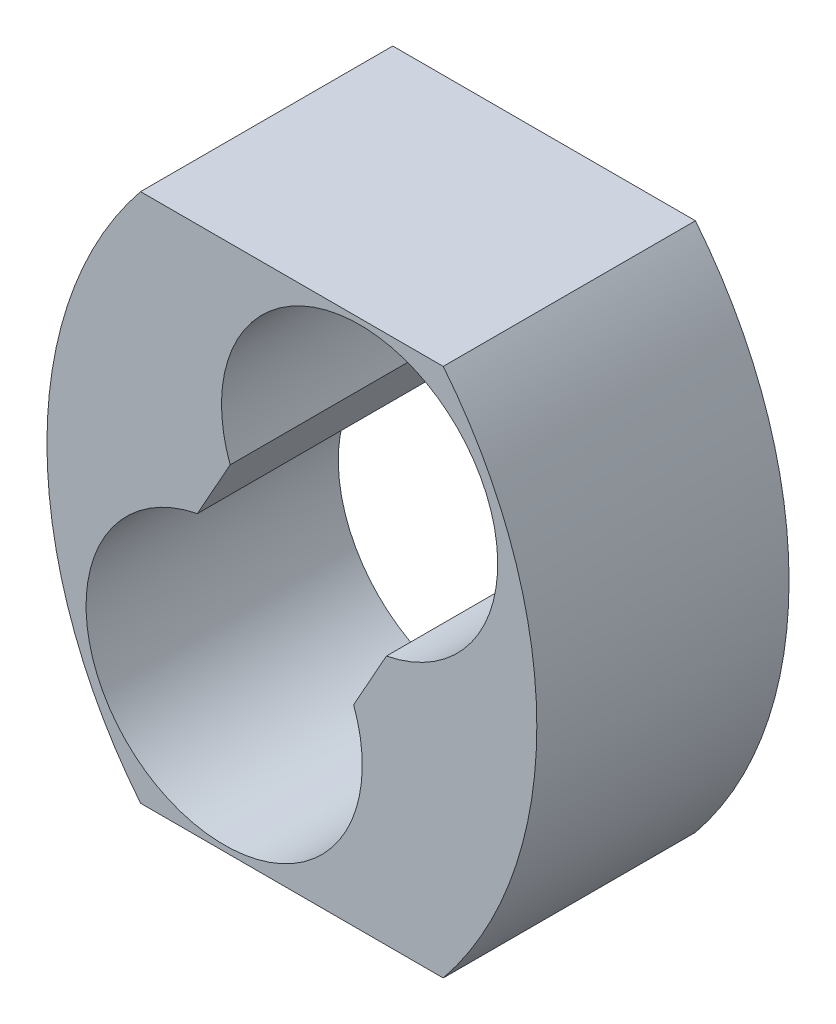
SolidWorks part; units mm, degrees
ref_plane "Alzado" through (0, 0, 0) normal (0, 0, 1) x (1, 0, 0)
ref_plane "Planta" through (0, 0, 0) normal (0, 1, 0) x (1, 0, 0)
ref_plane "Vista lateral" through (0, 0, 0) normal (1, 0, 0) x (0, 0, -1)
sketch "Croquis3" plane through (0, 0, 0) normal (0, 0, 1) x (1, 0, 0)
  line L0 (-6, 0) -> (8.4261, 0) construction
  line L1 (-6, -10.5) -> (6, -10.5)
  line L2 (-6, -10.5) -> (-6, 10.5) construction
  line L3 (-6, 10.5) -> (6, 10.5)
  line L4 (6, -10.5) -> (6, 10.5) construction
  line L5 (-6, -10.5) -> (6, 10.5) construction
  line L6 (-6, 10.5) -> (6, -10.5) construction
  line L7 (8.4261, 0) -> (-9.9548, 0) construction
  line L8 (-2.6851, -4.8) -> (2.6851, 4.8) construction
  line L9 (2.6851, 4.8) -> (-3.098, 1.733) construction
  line L10 (-3.098, 1.733) -> (0, 0) construction
  line L12 (2.4483, -2.8945) -> (3.7477, -0.5715)
  line L13 (-3.7477, 0.5715) -> (-2.4483, 2.8945)
  line L15 (2.4483, -2.8945) -> (-2.4483, 2.8945) construction
  line L16 (-3.7477, 0.5715) -> (3.7477, -0.5715) construction
  line L17 (-0.6497, -1.1615) -> (-0.6603, -1.1556)
  line L18 (0.6603, 1.1556) -> (0.6497, 1.1615)
  arc A2 (6, -10.5) -> (6, 10.5) centre (-7, 0) ccw
  arc A3 (-6, 10.5) -> (-6, -10.5) centre (7, 0) ccw
  circle A4 centre (-2.6851, -4.8) radius 5.5 construction
  circle A5 centre (2.6851, 4.8) radius 5.5 construction
  arc A6 (3.7477, -0.5715) -> (-2.4483, 2.8945) centre (2.6851, 4.8) ccw
  arc A7 (-3.7477, 0.5715) -> (2.4483, -2.8945) centre (-2.6851, -4.8) ccw
  point P0 (0, 0)
  dimension "D3" = 13
  dimension "D5" = 11
  dimension "D6" = 11
  dimension "D8" = 5.7
  dimension "D1" = 12
  dimension "D2" = 21
  dimension "D4" = 13
  dimension "D7" = 11
  dimension "D9" = 5.7
  dimension "D10" = 0
extrude "Saliente-Extruir4" add sketch "Croquis3" along normal blind 10 contours L3 A3 L1 A2 A7 L13 A6 L12 region at (-9.4247, 0, 0)
